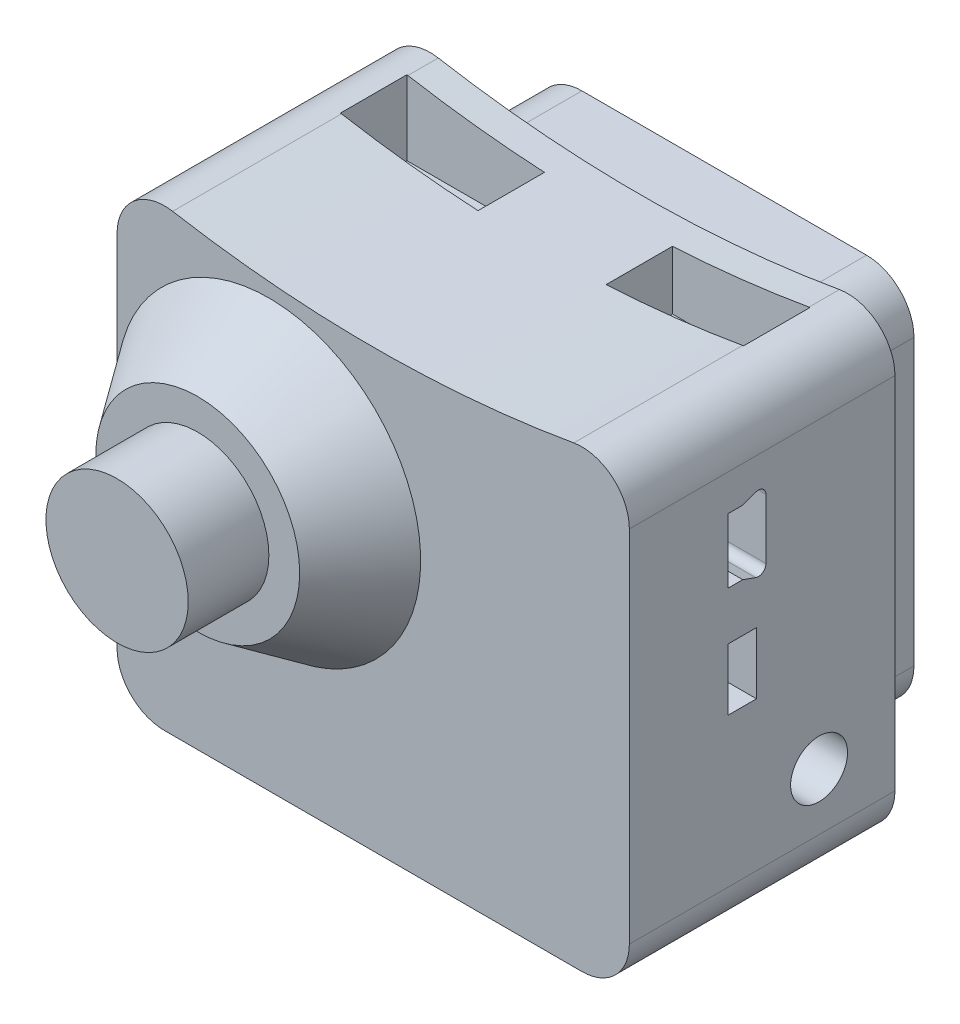
SolidWorks part; units mm, degrees
ref_plane "Plan de face" through (0, 0, 0) normal (0, 0, 1) x (1, 0, 0)
ref_plane "Plan de dessus" through (0, 0, 0) normal (0, 1, 0) x (1, 0, 0)
ref_plane "Plan de droite" through (0, 0, 0) normal (1, 0, 0) x (0, 0, -1)
sketch "Esquisse1" plane through (0, 0, 0) normal (0, 0, 1) x (1, 0, 0)
  line L0 (0, 0) -> (0, 34.0653) construction
  line L1 (-27, 0) -> (27, 0)
  line L2 (27, 0) -> (27, 49)
  line L3 (27, 49) -> (-27, 49) construction
  line L4 (-27, 49) -> (-27, 0)
  arc A0 (-27, 49) -> (27, 49) centre (0, 169) ccw
  point P6 (0, 46)
  dimension "D1" = 54
  dimension "D2" = 49
  dimension "D3" = 3
extrude "Boss.-Extru.1" add sketch "Esquisse1" along normal blind 28
sketch "Esquisse2" plane through (0, 0, 28) normal (0, 0, 1) x (1, 0, 0)
  line L0 (-27, 49) -> (-27, 0) construction
  line L1 (0, 46) -> (0, 0) construction
  line L2 (-27, 0) -> (27, 0) construction
  circle A0 centre (-11, 29) radius 7.5
  arc A1 (-27, 49) -> (27, 49) centre (0, 169) ccw construction
  dimension "D3" = 15
  dimension "D1" = 20
  dimension "D2" = 16
  dimension "D4" = 11
extrude "Boss.-Extru.2" add sketch "Esquisse2" along normal blind 16
sketch "Esquisse3" plane through (0, 0, 28) normal (0, 0, 1) x (1, 0, 0)
  circle A0 centre (-11, 29) radius 16
  circle A1 centre (-11, 29) radius 7.5 construction
  dimension "D1" = 32
extrude "Boss.-Extru.3" add sketch "Esquisse3" along normal blind 7.5
chamfer "Chanfrein2" distance 7.5 angle 35 1 edges at (5, 29, 35.5) first distance on face at (5, 29, 35.5)
sketch "Esquisse4" plane through (0, 0, 0) normal (0, -1, 0) x (1, 0, 0)
  line L0 (-27, 5.5) -> (27, 5.5) construction
  line L1 (-27, 28) -> (-27, 0) construction
  line L2 (27, 28) -> (27, 0) construction
  line L3 (0, 28) -> (0, 0) construction
  line L4 (-27, 28) -> (27, 28) construction
  circle A0 centre (-13, 5.5) radius 1.25
  circle A1 centre (13, 5.5) radius 1.25
  dimension "D1" = 2.5
  dimension "D2" = 26
  dimension "D3" = 22.5
extrude "Enlèv. mat.-Extru.1" cut sketch "Esquisse4" against normal blind 7.5
sketch "Esquisse5" plane through (0, 0, 0) normal (0, 0, -1) x (-1, 0, 0)
  line L0 (0, 0) -> (0, 46) construction
  line L1 (-20, 43.4) -> (20, 43.4)
  line L2 (-20, 43.4) -> (-20, 3.4)
  line L3 (-20, 3.4) -> (20, 3.4)
  line L4 (20, 43.4) -> (20, 3.4)
  line L5 (27, 0) -> (-27, 0) construction
  line L6 (20, 23.4) -> (-20, 23.4) construction
  arc A0 (-27, 49) -> (27, 49) centre (0, 169) ccw construction
  circle A1 centre (0, 23.4) radius 18.9
  circle A2 centre (0, 23.4) radius 10
  dimension "D4" = 37.8
  dimension "D5" = 20
  dimension "D1" = 3.4
  dimension "D2" = 40
  dimension "D3" = 40
extrude "Boss.-Extru.4" add sketch "Esquisse5" along normal blind 9 contours L4 L1 L2 L3 A1 | A2 region at (0, 42.8343, 0) region at (0, 23.4, 0)
ref_plane "Plan2" through (0, 49, 0) normal (0, 1, 0) x (1, 0, 0)
sketch "Esquisse7" plane through (0, 49, 0) normal (0, 1, 0) x (1, 0, 0)
  line L0 (-27, 0) -> (27, 0) construction
  line L1 (27, -28) -> (-27, -28) construction
  line L2 (0, 0) -> (0, -28) construction
  line L3 (-21.25, -3.2) -> (-6.75, -3.2)
  line L4 (-21.25, -3.2) -> (-21.25, -10.2)
  line L5 (-21.25, -10.2) -> (-6.75, -10.2)
  line L6 (-6.75, -3.2) -> (-6.75, -10.2)
  line L7 (6.75, -3.2) -> (21.25, -3.2)
  line L8 (6.75, -3.2) -> (6.75, -10.2)
  line L9 (6.75, -10.2) -> (21.25, -10.2)
  line L10 (21.25, -3.2) -> (21.25, -10.2)
  dimension "D1" = 14.5
  dimension "D2" = 7
  dimension "D3" = 3.2
  dimension "D4" = 13.5
extrude "Enlèv. mat.-Extru.2" cut sketch "Esquisse7" against normal blind 9
sketch "Esquisse8" plane through (-27, 0, 0) normal (-1, 0, 0) x (0, 0, 1)
  line L0 (14.6, 27) -> (14.6, 20.5)
  line L1 (14.6, 20.5) -> (16.6, 20.5)
  line L2 (14.6, 27) -> (16.6, 27)
  line L3 (17.6, 26) -> (17.6, 21.5)
  line L4 (28, 49) -> (0, 49) construction
  line L6 (0, 0) -> (0, 49) construction
  line L7 (14.6, 29) -> (17.6, 29)
  line L8 (14.6, 29) -> (14.6, 39)
  line L9 (14.6, 39) -> (17.6, 39)
  line L10 (17.6, 29) -> (17.6, 39)
  arc A0 (16.6, 27) -> (17.6, 26) centre (16.6, 26) cw
  arc A1 (17.6, 21.5) -> (16.6, 20.5) centre (16.6, 21.5) cw
  dimension "D3" = 1
  dimension "D4" = 1
  dimension "D1" = 6.5
  dimension "D2" = 3
  dimension "D5" = 22
  dimension "D6" = 17.6
  dimension "D7" = 2
  dimension "D8" = 10
extrude "Enlèv. mat.-Extru.3" cut sketch "Esquisse8" against normal blind 9
sketch "Esquisse9" plane through (27, 0, 0) normal (1, 0, 0) x (0, 0, -1)
  line L0 (0, 0) -> (0, 49) construction
  line L3 (-17.6, 39.1) -> (-17.6, 32.3)
  line L4 (-17.6, 32.3) -> (-15.1594, 32.3) construction
  line L6 (-13.6, 38.8482) -> (-13.6, 32.5518)
  line L7 (-17.6, 39.1) -> (-15.1594, 39.1) construction
  line L8 (-17.6, 35.7) -> (-13.6, 35.7) construction
  line L10 (-16.0474, 39.1) -> (-14.6736, 39.6)
  line L11 (-17.6, 39.1) -> (-16.0474, 39.1)
  line L12 (-17.6, 32.3) -> (-16.0474, 32.3)
  line L13 (-16.0474, 32.3) -> (-14.6736, 31.8)
  line L14 (15.4, 49) -> (-15.4, 49) construction
  line L16 (-17.6, 27.2) -> (-14.6, 27.2)
  line L17 (-17.6, 27.2) -> (-17.6, 20.7)
  line L18 (-17.6, 20.7) -> (-14.6, 20.7)
  line L19 (-14.6, 27.2) -> (-14.6, 20.7)
  circle A0 centre (-8, 11) radius 3
  arc A1 (-15.1594, 39.1) -> (-13.6, 38.8482) centre (-14.4, 38.8482) cw construction
  arc A2 (-15.1594, 32.3) -> (-13.6, 32.5518) centre (-14.4, 32.5518) ccw construction
  arc A3 (-14.6736, 39.6) -> (-13.6, 38.8482) centre (-14.4, 38.8482) cw
  arc A4 (-14.6736, 31.8) -> (-13.6, 32.5518) centre (-14.4, 32.5518) ccw
  dimension "D3" = 6
  dimension "D8" = 0.8
  dimension "D1" = 8
  dimension "D2" = 11
  dimension "D4" = 6.8
  dimension "D5" = 0.5
  dimension "D6" = 20
  dimension "D7" = 4
  dimension "D9" = 17.6
  dimension "D10" = 13.3
  dimension "D11" = 3
  dimension "D12" = 6.5
  dimension "D13" = 21.8
extrude "Enlèv. mat.-Extru.4" cut sketch "Esquisse9" against normal blind 9
fillet "Congé2" radius 5 8 edges at (20, 3.4, -4.5) (-20, 3.4, -4.5) (-20, 43.4, -4.5) (20, 43.4, -4.5) (-27, 49, 14) (-27, 0, 14) (27, 0, 14) (27, 49, 14)
